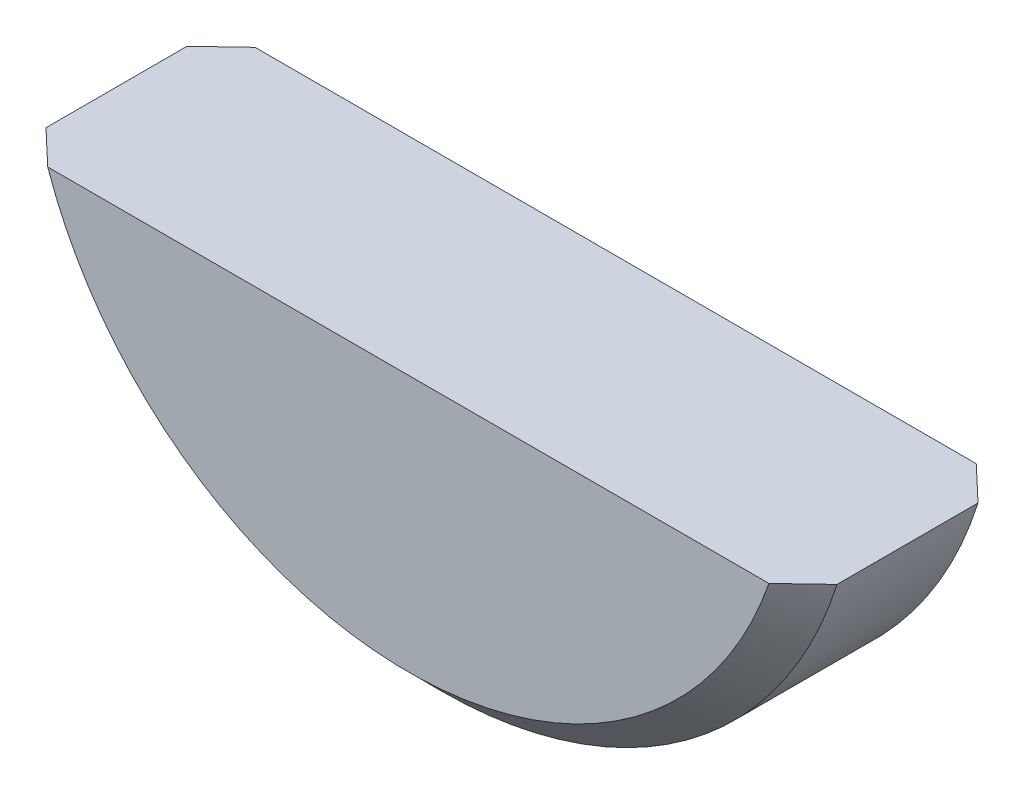
SolidWorks part; units mm, degrees
ref_plane "Front Plane" through (0, 0, 0) normal (0, 0, 1) x (1, 0, 0)
ref_plane "Top Plane" through (0, 0, 0) normal (0, 1, 0) x (1, 0, 0)
ref_plane "Right Plane" through (0, 0, 0) normal (1, 0, 0) x (0, 0, -1)
sketch "BodySke" plane through (0, 0, 0) normal (0, 0, 1) x (1, 0, 0)
  line L0 (0, 0) -> (0, 8.1206) construction
  line L1 (-1.9079, 1.4) -> (1.9079, 1.4)
  line L2 (-1.0536, 0.3) -> (1.0536, 0.3) construction
  arc A0 (-1.9079, 1.4) -> (1.9079, 1.4) centre (0, 2) ccw
  dimension "Key_Diameter" = 4
  dimension "Height_normal" = 1.4
  dimension "Height_whitney" = 1.1
extrude "BaseBody" add sketch "BodySke" along normal blind 1
chamfer "Chamfer" distance 0.16 angle 45 2 edges at (0, 0, 0) (0, 0, 1)
sketch "WhitneySke" plane through (0, 0, 0) normal (0, 0, 1) x (1, 0, 0)
  line L0 (0, 0) -> (0, 1.9557) construction
  line L1 (0, 0) -> (0, 8.1206) construction
  line L2 (-1.0536, 0.3) -> (1.0536, 0.3) construction
  line L3 (-1.0536, 0.3) -> (1.0536, 0.3)
  arc A0 (-1.9079, 1.4) -> (1.9079, 1.4) centre (0, 2) ccw construction
  arc A1 (-1.0536, 0.3) -> (1.0536, 0.3) centre (0, 2) ccw
extrude "Whitney" [suppressed] cut sketch "WhitneySke" along normal through all
